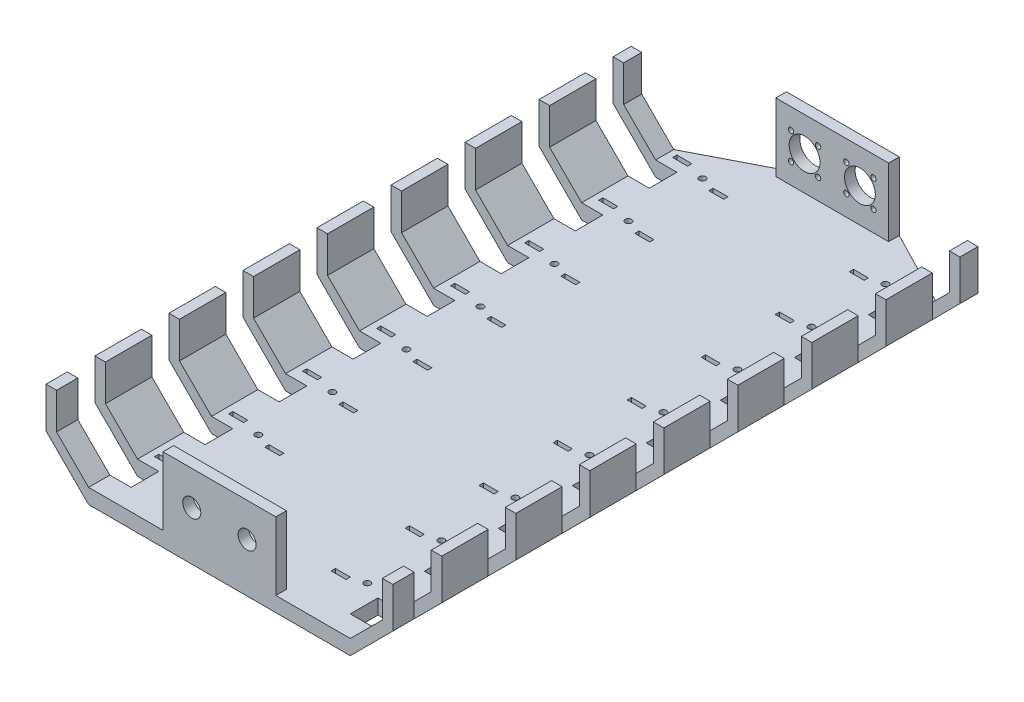
SolidWorks part; units mm, degrees
ref_plane "Front Plane" through (0, 0, 0) normal (0, 0, 1) x (1, 0, 0)
ref_plane "Top Plane" through (0, 0, 0) normal (0, 1, 0) x (1, 0, 0)
ref_plane "Right Plane" through (0, 0, 0) normal (1, 0, 0) x (0, 0, -1)
sketch "Sketch1" plane through (0, 0, 0) normal (0, 1, 0) x (1, 0, 0)
  line L0 (0, -135) -> (0, 135) construction
  line L1 (-13, 135) -> (-36, 135)
  line L2 (13, -135) -> (-13, -135)
  line L3 (13, -135) -> (13, 135) construction
  line L4 (13, 135) -> (-13, 135)
  line L5 (-13, -135) -> (-13, 135) construction
  line L8 (-36, 135) -> (-36, -135) construction
  line L9 (-36, -135) -> (-13, -135)
  line L10 (-36, 135) -> (-61.5, 135)
  line L11 (-61.5, 135) -> (-61.5, -135)
  line L12 (-61.5, -135) -> (-36, -135)
  line L13 (36, -135) -> (13, -135)
  line L14 (61.5, -135) -> (36, -135)
  line L15 (61.5, 135) -> (61.5, -135)
  line L16 (36, 135) -> (36, -135) construction
  line L17 (13, 135) -> (36, 135)
  line L18 (36, 135) -> (61.5, 135)
  point P0 (0, 0)
  point P4 (0, 0)
  dimension "D1" = 270
  dimension "D2" = 26
  dimension "D3" = 23
  dimension "D4" = 123
extrude "Boss-Extrude1" add sketch "Sketch1" along normal blind 7
sketch "Sketch2" plane through (0, 7, 0) normal (0, 1, 0) x (1, 0, 0)
  line L0 (61.5, -135) -> (61.5, 135) construction
  line L1 (-61.5, -135) -> (61.5, -135)
  line L2 (-61.5, -135) -> (-61.5, -130)
  line L3 (-61.5, -130) -> (61.5, -130)
  line L4 (61.5, -135) -> (61.5, -130)
  line L21 (-26.5, 130) -> (-26.5, -130) construction
  dimension "D1" = 5
extrude "Boss-Extrude2" add sketch "Sketch2" along normal blind 32
sketch "Sketch3" plane through (0, 0, 135) normal (0, 0, 1) x (1, 0, 0)
  line L0 (0, 39) -> (0, 0) construction
  line L2 (-61.5, 39) -> (-61.5, 7) construction
  line L3 (-61.5, 39) -> (61.5, 39) construction
  line L5 (-61.5, 39) -> (-61.5, 0) construction
  line L6 (-61.5, 23) -> (61.5, 23) construction
  line L7 (61.5, 39) -> (61.5, 0) construction
  circle A0 centre (-13, 23) radius 4.25
  circle A1 centre (13, 23) radius 4.25
  dimension "D1" = 8.5
  dimension "D2" = 8.5
  dimension "D3" = 26
  dimension "D4" = 13
  dimension "D5" = 32
  dimension "D6" = 16
sketch "Sketch9" plane through (0, 0, -135) normal (0, 0, -1) x (-1, 0, 0)
  line L1 (-61.5, 7) -> (61.5, 7)
  line L2 (-61.5, 7) -> (-61.5, 0)
  line L3 (-61.5, 0) -> (61.5, 0)
  line L4 (61.5, 7) -> (61.5, 0)
extrude "Boss-Extrude4" add sketch "Sketch9" along normal blind 5
sketch "Sketch13" plane through (0, 0, 135) normal (0, 0, 1) x (1, 0, 0)
  line L0 (-61.5, 39) -> (-61.5, 7)
  line L1 (-61.5, 39) -> (-61.5, 0) construction
  line L2 (-61.5, 39) -> (-26.5, 39)
  line L3 (-61.5, 39) -> (61.5, 39) construction
  line L4 (-26.5, 39) -> (-26.5, 7)
  line L5 (-26.5, 7) -> (-61.5, 7)
  line L6 (0, 39) -> (0, 5.5161) construction
  line L7 (26.5, 39) -> (26.5, 7)
  line L8 (61.5, 39) -> (26.5, 39)
  line L9 (61.5, 39) -> (61.5, 7)
  line L10 (26.5, 7) -> (61.5, 7)
  dimension "D1" = 32
  dimension "D2" = 35
extrude "Cut-Extrude5" cut sketch "Sketch13" against normal blind 11
sketch "Sketch14" plane through (0, 0, 135) normal (0, 0, 1) x (1, 0, 0)
  line L0 (0, 39) -> (0, 0) construction
  line L1 (-26.5, 39) -> (26.5, 39) construction
  line L2 (-81.5, 39) -> (0, 39) construction
  line L3 (-61.5, 0) -> (-81.5, 20)
  line L5 (-76.55, 22.05) -> (-61.5, 7)
  line L7 (-61.5, 7) -> (-61.5, 0)
  line L12 (-81.5, 20) -> (-81.5, 39)
  line L13 (-81.5, 39) -> (-76.55, 39)
  line L14 (-76.55, 39) -> (-76.55, 22.05)
  line L15 (76.55, 39) -> (76.55, 22.05)
  line L16 (81.5, 39) -> (76.55, 39)
  line L17 (81.5, 20) -> (81.5, 39)
  line L18 (61.5, 0) -> (81.5, 20)
  line L19 (61.5, 7) -> (61.5, 0)
  line L20 (76.55, 22.05) -> (61.5, 7)
  line L21 (-61.5, 7) -> (-61.5, 39) construction
  dimension "D1" = 28.2843
  dimension "D2" = 45
  dimension "D3" = 4.95
  dimension "D4" = 20
  dimension "D5" = 4.9497
  dimension "D6" = 21.2839
extrude "Boss-Extrude10" add sketch "Sketch14" against normal blind 275
sketch "Sketch17" plane through (0, 7, 0) normal (0, 1, 0) x (1, 0, 0)
  line L0 (-26.5, 130) -> (26.5, 130) construction
  line L1 (0, 130) -> (0, 161) construction
  line L2 (-26.5, -135) -> (-26.5, 161) construction
  line L3 (26.5, -135) -> (26.5, 161) construction
  line L4 (26.5, 161) -> (-26.5, 161) construction
  line L5 (0, 161) -> (0, 226) construction
  line L6 (-61.5, 140) -> (-26.5, 226)
  line L7 (-26.5, 226) -> (0, 226)
  line L8 (0, 226) -> (26.5, 226)
  line L9 (26.5, 226) -> (61.5, 140)
  line L10 (26.5, 161) -> (26.5, 226) construction
  line L11 (-26.5, 161) -> (-26.5, 226) construction
  line L12 (-61.5, 140) -> (61.5, 140)
  line L13 (-61.5, 140) -> (61.5, 140) construction
  dimension "D1" = 31
  dimension "D2" = 296
  dimension "D3" = 90
  dimension "D4" = 65
  dimension "D5" = 10
extrude "Boss-Extrude13" add sketch "Sketch17" against normal blind 7 contours L12 L9 L8 L7 L6
sketch "Sketch18" plane through (0, 7, 0) normal (0, 1, 0) x (1, 0, 0)
  line L0 (-26.5, 127) -> (26.5, 127) construction
  line L1 (0, 127) -> (0, 158) construction
  line L2 (-26.5, 135) -> (-26.5, 158) construction
  line L3 (26.5, 132) -> (26.5, 158) construction
  line L4 (-26.5, 158) -> (-26.5, 153)
  line L5 (-26.5, 153) -> (26.5, 153)
  line L6 (26.5, 153) -> (26.5, 158)
  line L7 (26.5, 158) -> (-26.5, 158)
  line L8 (-61.5, 140) -> (-61.5, -135) construction
  line L10 (76.55, 140) -> (61.5, 140) construction
  dimension "D1" = 31
  dimension "D2" = 5
  dimension "D3" = 35
  dimension "D4" = 53
  dimension "D5" = 13
extrude "Boss-Extrude14" add sketch "Sketch18" along normal blind 32
extrude "Cut-Extrude8" cut sketch "Sketch3" against normal blind 334
sketch "Sketch19" plane through (0, 0, -153) normal (0, 0, 1) x (1, 0, 0)
  line L0 (0, 39) -> (0, 0) construction
  line L1 (-26.5, 39) -> (26.5, 39) construction
  line L3 (-6.636, 16.636) -> (-19.364, 16.636) construction
  line L4 (-6.636, 16.636) -> (-6.636, 29.364) construction
  line L5 (-6.636, 29.364) -> (-19.364, 29.364) construction
  line L6 (-19.364, 16.636) -> (-19.364, 29.364) construction
  line L7 (-6.636, 16.636) -> (-19.364, 29.364) construction
  line L8 (-6.636, 29.364) -> (-19.364, 16.636) construction
  circle A0 centre (-13, 23) radius 7.25
  circle A1 centre (-6.636, 16.636) radius 1.25
  circle A2 centre (-6.636, 29.364) radius 1.25
  circle A3 centre (-19.364, 29.364) radius 1.25
  circle A4 centre (-19.364, 16.636) radius 1.25
  circle A5 centre (13, 23) radius 7.25
  circle A6 centre (19.364, 16.636) radius 1.25
  circle A7 centre (6.636, 16.636) radius 1.25
  circle A8 centre (6.636, 29.364) radius 1.25
  circle A9 centre (19.364, 29.364) radius 1.25
  dimension "D1" = 14.5
  dimension "D4" = 2.5
  dimension "D5" = 2.5
  dimension "D6" = 2.5
  dimension "D7" = 2.5
  dimension "D2" = 18
  dimension "D3" = 18
  dimension "D8" = 12.7279
extrude "Cut-Extrude9" cut sketch "Sketch19" against normal blind 334
sketch "Sketch29" plane through (0, 7, 0) normal (0, 1, 0) x (1, 0, 0)
  line L0 (-61.5, 140) -> (-26.5, 158)
  line L1 (-26.5, 158) -> (26.5, 158)
  line L2 (26.5, 158) -> (61.5, 140)
  line L3 (61.5, 140) -> (26.5, 226)
  line L4 (26.5, 226) -> (-26.5, 226)
  line L5 (-26.5, 226) -> (-61.5, 140)
extrude "Cut-Extrude13" cut sketch "Sketch29" against normal blind 19
sketch "Sketch32" plane through (0, 7, 0) normal (0, 1, 0) x (1, 0, 0)
  line L0 (-61.5, 137.5) -> (-55, 137.5) construction
  line L1 (-61.5, 140) -> (-26.5, 140) construction
  line L2 (-81.5, 140) -> (-81.5, -135) construction
  line L3 (-61.5, 140) -> (-61.5, 130) construction
  line L4 (0, 158) -> (0, -135) construction
  line L5 (26.5, 158) -> (-26.5, 158) construction
  line L6 (-26.5, -135) -> (26.5, -135) construction
  line L7 (-61.5, 130) -> (-26.5, 130) construction
  line L8 (-81.5, 131.5) -> (-51.5, 131.5)
  line L9 (-26.5, 140) -> (-26.5, 130) construction
  line L10 (-81.5, 131.5) -> (-81.5, 118.5)
  line L11 (-51.5, 136.5) -> (-58.5, 136.5)
  line L12 (-51.5, 136.5) -> (-51.5, 138.5)
  line L13 (-51.5, 138.5) -> (-58.5, 138.5)
  line L14 (-58.5, 136.5) -> (-58.5, 138.5)
  line L15 (-51.5, 136.5) -> (-58.5, 138.5) construction
  line L16 (-51.5, 138.5) -> (-58.5, 136.5) construction
  line L17 (-29.5, 131.5) -> (-36.5, 131.5)
  line L18 (-29.5, 131.5) -> (-29.5, 133.5)
  line L19 (-29.5, 133.5) -> (-36.5, 133.5)
  line L20 (-36.5, 131.5) -> (-36.5, 133.5)
  line L21 (-29.5, 131.5) -> (-36.5, 133.5) construction
  line L22 (-29.5, 133.5) -> (-36.5, 131.5) construction
  line L23 (-81.5, 118.5) -> (-51.5, 118.5)
  line L24 (-51.5, 131.5) -> (-51.5, 118.5)
  line L25 (-81.5, 96.7143) -> (-81.5, 83.7143)
  line L26 (-81.5, 96.7143) -> (-51.5, 96.7143)
  line L27 (-51.5, 96.7143) -> (-51.5, 83.7143)
  line L28 (-81.5, 83.7143) -> (-51.5, 83.7143)
  line L29 (-51.5, 101.7143) -> (-51.5, 103.7143)
  line L30 (-51.5, 101.7143) -> (-58.5, 101.7143)
  line L31 (-58.5, 101.7143) -> (-58.5, 103.7143)
  line L32 (-51.5, 103.7143) -> (-58.5, 103.7143)
  line L33 (-29.5, 96.7143) -> (-29.5, 98.7143)
  line L34 (-29.5, 96.7143) -> (-36.5, 96.7143)
  line L35 (-36.5, 96.7143) -> (-36.5, 98.7143)
  line L36 (-29.5, 98.7143) -> (-36.5, 98.7143)
  line L37 (-81.5, 61.9286) -> (-81.5, 48.9286)
  line L38 (-81.5, 61.9286) -> (-51.5, 61.9286)
  line L39 (-51.5, 61.9286) -> (-51.5, 48.9286)
  line L40 (-81.5, 48.9286) -> (-51.5, 48.9286)
  line L41 (-51.5, 66.9286) -> (-51.5, 68.9286)
  line L42 (-51.5, 66.9286) -> (-58.5, 66.9286)
  line L43 (-58.5, 66.9286) -> (-58.5, 68.9286)
  line L44 (-51.5, 68.9286) -> (-58.5, 68.9286)
  line L45 (-29.5, 61.9286) -> (-29.5, 63.9286)
  line L46 (-29.5, 61.9286) -> (-36.5, 61.9286)
  line L47 (-36.5, 61.9286) -> (-36.5, 63.9286)
  line L48 (-29.5, 63.9286) -> (-36.5, 63.9286)
  line L49 (-81.5, 27.1429) -> (-81.5, 14.1429)
  line L50 (-81.5, 27.1429) -> (-51.5, 27.1429)
  line L51 (-51.5, 27.1429) -> (-51.5, 14.1429)
  line L52 (-81.5, 14.1429) -> (-51.5, 14.1429)
  line L53 (-51.5, 32.1429) -> (-51.5, 34.1429)
  line L54 (-51.5, 32.1429) -> (-58.5, 32.1429)
  line L55 (-58.5, 32.1429) -> (-58.5, 34.1429)
  line L56 (-51.5, 34.1429) -> (-58.5, 34.1429)
  line L57 (-29.5, 27.1429) -> (-29.5, 29.1429)
  line L58 (-29.5, 27.1429) -> (-36.5, 27.1429)
  line L59 (-36.5, 27.1429) -> (-36.5, 29.1429)
  line L60 (-29.5, 29.1429) -> (-36.5, 29.1429)
  line L61 (-81.5, -7.6429) -> (-81.5, -20.6429)
  line L62 (-81.5, -7.6429) -> (-51.5, -7.6429)
  line L63 (-51.5, -7.6429) -> (-51.5, -20.6429)
  line L64 (-81.5, -20.6429) -> (-51.5, -20.6429)
  line L65 (-51.5, -2.6429) -> (-51.5, -0.6429)
  line L66 (-51.5, -2.6429) -> (-58.5, -2.6429)
  line L67 (-58.5, -2.6429) -> (-58.5, -0.6429)
  line L68 (-51.5, -0.6429) -> (-58.5, -0.6429)
  line L69 (-29.5, -7.6429) -> (-29.5, -5.6429)
  line L70 (-29.5, -7.6429) -> (-36.5, -7.6429)
  line L71 (-36.5, -7.6429) -> (-36.5, -5.6429)
  line L72 (-29.5, -5.6429) -> (-36.5, -5.6429)
  line L73 (-81.5, -42.4286) -> (-81.5, -55.4286)
  line L74 (-81.5, -42.4286) -> (-51.5, -42.4286)
  line L75 (-51.5, -42.4286) -> (-51.5, -55.4286)
  line L76 (-81.5, -55.4286) -> (-51.5, -55.4286)
  line L77 (-51.5, -37.4286) -> (-51.5, -35.4286)
  line L78 (-51.5, -37.4286) -> (-58.5, -37.4286)
  line L79 (-58.5, -37.4286) -> (-58.5, -35.4286)
  line L80 (-51.5, -35.4286) -> (-58.5, -35.4286)
  line L81 (-29.5, -42.4286) -> (-29.5, -40.4286)
  line L82 (-29.5, -42.4286) -> (-36.5, -42.4286)
  line L83 (-36.5, -42.4286) -> (-36.5, -40.4286)
  line L84 (-29.5, -40.4286) -> (-36.5, -40.4286)
  line L85 (-81.5, -77.2143) -> (-81.5, -90.2143)
  line L86 (-81.5, -77.2143) -> (-51.5, -77.2143)
  line L87 (-51.5, -77.2143) -> (-51.5, -90.2143)
  line L88 (-81.5, -90.2143) -> (-51.5, -90.2143)
  line L89 (-51.5, -72.2143) -> (-51.5, -70.2143)
  line L90 (-51.5, -72.2143) -> (-58.5, -72.2143)
  line L91 (-58.5, -72.2143) -> (-58.5, -70.2143)
  line L92 (-51.5, -70.2143) -> (-58.5, -70.2143)
  line L93 (-29.5, -77.2143) -> (-29.5, -75.2143)
  line L94 (-29.5, -77.2143) -> (-36.5, -77.2143)
  line L95 (-36.5, -77.2143) -> (-36.5, -75.2143)
  line L96 (-29.5, -75.2143) -> (-36.5, -75.2143)
  line L97 (-81.5, -112) -> (-81.5, -125)
  line L98 (-81.5, -112) -> (-51.5, -112)
  line L99 (-51.5, -112) -> (-51.5, -125)
  line L100 (-81.5, -125) -> (-51.5, -125)
  line L101 (-51.5, -107) -> (-51.5, -105)
  line L102 (-51.5, -107) -> (-58.5, -107)
  line L103 (-58.5, -107) -> (-58.5, -105)
  line L104 (-51.5, -105) -> (-58.5, -105)
  line L105 (-29.5, -112) -> (-29.5, -110)
  line L106 (-29.5, -112) -> (-36.5, -112)
  line L107 (-36.5, -112) -> (-36.5, -110)
  line L108 (-29.5, -110) -> (-36.5, -110)
  line L109 (-26.5, -130) -> (-26.5, -125) construction
  line L110 (-26.5, -125) -> (-51.5, -125) construction
  line L111 (26.5, -125) -> (51.5, -125) construction
  line L112 (26.5, -130) -> (26.5, -125) construction
  line L113 (29.5, 133.5) -> (36.5, 131.5) construction
  line L114 (29.5, 131.5) -> (36.5, 133.5) construction
  line L115 (51.5, 138.5) -> (58.5, 136.5) construction
  line L116 (51.5, 136.5) -> (58.5, 138.5) construction
  line L117 (26.5, 140) -> (26.5, 130) construction
  line L118 (61.5, 130) -> (26.5, 130) construction
  line L119 (61.5, 140) -> (61.5, 130) construction
  line L120 (61.5, 140) -> (26.5, 140) construction
  line L121 (61.5, 137.5) -> (55, 137.5) construction
  line L122 (29.5, -110) -> (36.5, -110)
  line L123 (36.5, -112) -> (36.5, -110)
  line L124 (29.5, -112) -> (36.5, -112)
  line L125 (29.5, -112) -> (29.5, -110)
  line L126 (51.5, -105) -> (58.5, -105)
  line L127 (58.5, -107) -> (58.5, -105)
  line L128 (51.5, -107) -> (58.5, -107)
  line L129 (51.5, -107) -> (51.5, -105)
  line L130 (81.5, -125) -> (51.5, -125)
  line L131 (51.5, -112) -> (51.5, -125)
  line L132 (81.5, -112) -> (51.5, -112)
  line L133 (81.5, -112) -> (81.5, -125)
  line L134 (29.5, -75.2143) -> (36.5, -75.2143)
  line L135 (36.5, -77.2143) -> (36.5, -75.2143)
  line L136 (29.5, -77.2143) -> (36.5, -77.2143)
  line L137 (29.5, -77.2143) -> (29.5, -75.2143)
  line L138 (51.5, -70.2143) -> (58.5, -70.2143)
  line L139 (58.5, -72.2143) -> (58.5, -70.2143)
  line L140 (51.5, -72.2143) -> (58.5, -72.2143)
  line L141 (51.5, -72.2143) -> (51.5, -70.2143)
  line L142 (81.5, -90.2143) -> (51.5, -90.2143)
  line L143 (51.5, -77.2143) -> (51.5, -90.2143)
  line L144 (81.5, -77.2143) -> (51.5, -77.2143)
  line L145 (81.5, -77.2143) -> (81.5, -90.2143)
  line L146 (29.5, -40.4286) -> (36.5, -40.4286)
  line L147 (36.5, -42.4286) -> (36.5, -40.4286)
  line L148 (29.5, -42.4286) -> (36.5, -42.4286)
  line L149 (29.5, -42.4286) -> (29.5, -40.4286)
  line L150 (51.5, -35.4286) -> (58.5, -35.4286)
  line L151 (58.5, -37.4286) -> (58.5, -35.4286)
  line L152 (51.5, -37.4286) -> (58.5, -37.4286)
  line L153 (51.5, -37.4286) -> (51.5, -35.4286)
  line L154 (81.5, -55.4286) -> (51.5, -55.4286)
  line L155 (51.5, -42.4286) -> (51.5, -55.4286)
  line L156 (81.5, -42.4286) -> (51.5, -42.4286)
  line L157 (81.5, -42.4286) -> (81.5, -55.4286)
  line L158 (29.5, -5.6429) -> (36.5, -5.6429)
  line L159 (36.5, -7.6429) -> (36.5, -5.6429)
  line L160 (29.5, -7.6429) -> (36.5, -7.6429)
  line L161 (29.5, -7.6429) -> (29.5, -5.6429)
  line L162 (51.5, -0.6429) -> (58.5, -0.6429)
  line L163 (58.5, -2.6429) -> (58.5, -0.6429)
  line L164 (51.5, -2.6429) -> (58.5, -2.6429)
  line L165 (51.5, -2.6429) -> (51.5, -0.6429)
  line L166 (81.5, -20.6429) -> (51.5, -20.6429)
  line L167 (51.5, -7.6429) -> (51.5, -20.6429)
  line L168 (81.5, -7.6429) -> (51.5, -7.6429)
  line L169 (81.5, -7.6429) -> (81.5, -20.6429)
  line L170 (29.5, 29.1429) -> (36.5, 29.1429)
  line L171 (36.5, 27.1429) -> (36.5, 29.1429)
  line L172 (29.5, 27.1429) -> (36.5, 27.1429)
  line L173 (29.5, 27.1429) -> (29.5, 29.1429)
  line L174 (51.5, 34.1429) -> (58.5, 34.1429)
  line L175 (58.5, 32.1429) -> (58.5, 34.1429)
  line L176 (51.5, 32.1429) -> (58.5, 32.1429)
  line L177 (51.5, 32.1429) -> (51.5, 34.1429)
  line L178 (81.5, 14.1429) -> (51.5, 14.1429)
  line L179 (51.5, 27.1429) -> (51.5, 14.1429)
  line L180 (81.5, 27.1429) -> (51.5, 27.1429)
  line L181 (81.5, 27.1429) -> (81.5, 14.1429)
  line L182 (29.5, 63.9286) -> (36.5, 63.9286)
  line L183 (36.5, 61.9286) -> (36.5, 63.9286)
  line L184 (29.5, 61.9286) -> (36.5, 61.9286)
  line L185 (29.5, 61.9286) -> (29.5, 63.9286)
  line L186 (51.5, 68.9286) -> (58.5, 68.9286)
  line L187 (58.5, 66.9286) -> (58.5, 68.9286)
  line L188 (51.5, 66.9286) -> (58.5, 66.9286)
  line L189 (51.5, 66.9286) -> (51.5, 68.9286)
  line L190 (81.5, 48.9286) -> (51.5, 48.9286)
  line L191 (51.5, 61.9286) -> (51.5, 48.9286)
  line L192 (81.5, 61.9286) -> (51.5, 61.9286)
  line L193 (81.5, 61.9286) -> (81.5, 48.9286)
  line L194 (29.5, 98.7143) -> (36.5, 98.7143)
  line L195 (36.5, 96.7143) -> (36.5, 98.7143)
  line L196 (29.5, 96.7143) -> (36.5, 96.7143)
  line L197 (29.5, 96.7143) -> (29.5, 98.7143)
  line L198 (51.5, 103.7143) -> (58.5, 103.7143)
  line L199 (58.5, 101.7143) -> (58.5, 103.7143)
  line L200 (51.5, 101.7143) -> (58.5, 101.7143)
  line L201 (51.5, 101.7143) -> (51.5, 103.7143)
  line L202 (81.5, 83.7143) -> (51.5, 83.7143)
  line L203 (51.5, 96.7143) -> (51.5, 83.7143)
  line L204 (81.5, 96.7143) -> (51.5, 96.7143)
  line L205 (81.5, 96.7143) -> (81.5, 83.7143)
  line L206 (51.5, 131.5) -> (51.5, 118.5)
  line L207 (81.5, 118.5) -> (51.5, 118.5)
  line L208 (36.5, 131.5) -> (36.5, 133.5)
  line L209 (29.5, 133.5) -> (36.5, 133.5)
  line L210 (29.5, 131.5) -> (29.5, 133.5)
  line L211 (29.5, 131.5) -> (36.5, 131.5)
  line L212 (58.5, 136.5) -> (58.5, 138.5)
  line L213 (51.5, 138.5) -> (58.5, 138.5)
  line L214 (51.5, 136.5) -> (51.5, 138.5)
  line L215 (51.5, 136.5) -> (58.5, 136.5)
  line L216 (81.5, 131.5) -> (81.5, 118.5)
  line L217 (81.5, 131.5) -> (51.5, 131.5)
  circle A0 centre (-43, 135) radius 1.5
  circle A1 centre (-43, 100.2143) radius 1.5
  circle A2 centre (-43, 65.4286) radius 1.5
  circle A3 centre (-43, 30.6429) radius 1.5
  circle A4 centre (-43, -4.1429) radius 1.5
  circle A5 centre (-43, -38.9286) radius 1.5
  circle A6 centre (-43, -73.7143) radius 1.5
  circle A7 centre (-43, -108.5) radius 1.5
  circle A8 centre (43, -108.5) radius 1.5
  circle A9 centre (43, -73.7143) radius 1.5
  circle A10 centre (43, -38.9286) radius 1.5
  circle A11 centre (43, -4.1429) radius 1.5
  circle A12 centre (43, 30.6429) radius 1.5
  circle A13 centre (43, 65.4286) radius 1.5
  circle A14 centre (43, 100.2143) radius 1.5
  circle A15 centre (43, 135) radius 1.5
  point P21 (-33, 132.5)
  point P131 (-51.2482, -125)
  point P252 (33, 132.5)
  dimension "D7" = 3
  dimension "D1" = 10
  dimension "D2" = 35
  dimension "D3" = 2
  dimension "D4" = 7
  dimension "D5" = 3
  dimension "D6" = 2.5
  dimension "D8" = 18.5
  dimension "D9" = 5
  dimension "D10" = 3
  dimension "D11" = 2.5
  dimension "D12" = 7
  dimension "D13" = 2
  dimension "D14" = 5
  dimension "D15" = 13
  dimension "D17" = 5
  dimension "D16" = 8
extrude "Cut-Extrude16" cut sketch "Sketch32" against normal through all both and the other way through all
